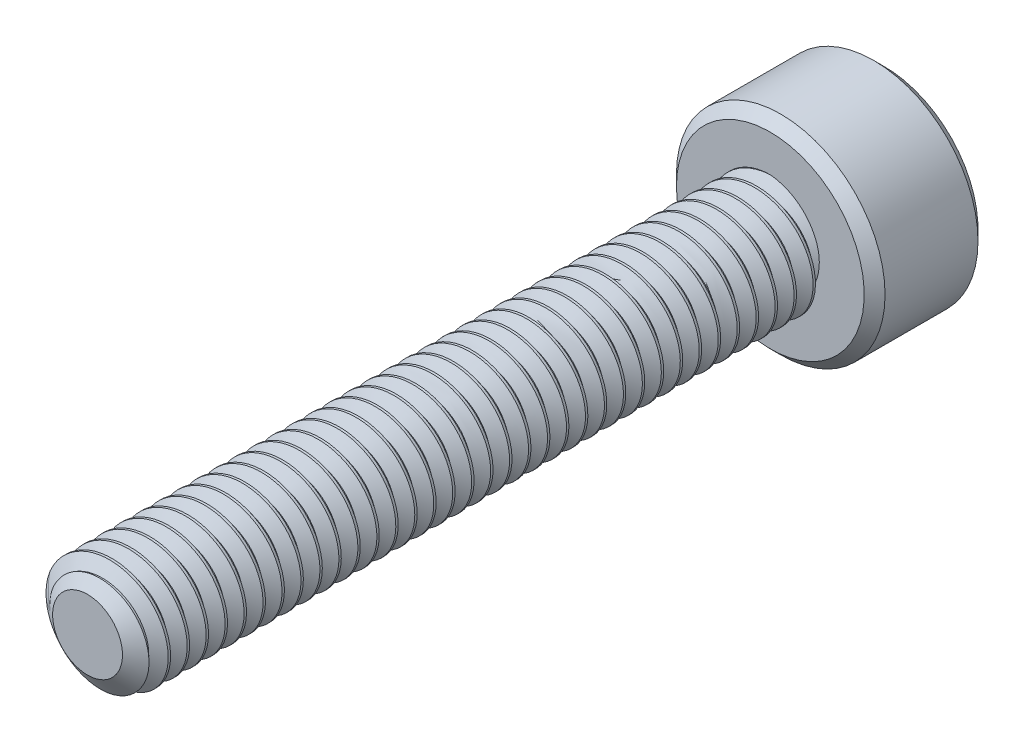
SolidWorks part; units mm, degrees
other "DetailItem1"
ref_plane "Front Plane" through (0, 0, 0) normal (0, 0, 1) x (1, 0, 0)
ref_plane "Top Plane" through (0, 0, 0) normal (0, 1, 0) x (1, 0, 0)
ref_plane "Right Plane" through (0, 0, 0) normal (1, 0, 0) x (0, 0, -1)
sketch "Sketch1" plane through (0, 0, 0) normal (0, 0, 1) x (1, 0, 0)
  circle A0 centre (0, 0) radius 1.5
  dimension "OD" = 3
extrude "Extrude1" add sketch "Sketch1" against normal blind 18
sketch "Sketch2" plane through (0, 0, 0) normal (0, 0, 1) x (1, 0, 0)
  circle A0 centre (0, 0) radius 1.5 construction
  circle A1 centre (0, 0) radius 1.5
curve "Helix/Spiral1" pitch 0.5 height 18.5 turns 37 parameters "pitch"=0.5
sketch "Sketch3" plane through (0, 0, 0) normal (1, 0, 0) x (0, 0, -1)
  line L0 (-0.4375, 1.5) -> (-0.25, 1.1752)
  line L1 (-0.25, 1.1752) -> (-0.1875, 1.1752)
  line L2 (-0.1875, 1.1752) -> (0, 1.5)
  line L3 (-0.4375, 1.5) -> (0, 1.5)
  line L4 (-0.2187, 1.5) -> (-0.2188, 1.1752) construction
  line L5 (-0.3438, 1.3376) -> (-0.0938, 1.3376) construction
  line L6 (0, 1.5) -> (0, -1.5) construction
  dimension "D1" = 0.0625
  dimension "D2" = 0.25
  dimension "D3" = 60
sweep "Cut-Sweep1" cut profiles "Sketch3" path "Helix/Spiral1" align with end faces yes
sketch "Sketch4" plane through (0, 0, 0) normal (1, 0, 0) x (0, 0, -1)
  line L0 (0.4053, 1.5) -> (0, 0.9212)
  line L1 (0, 0.9212) -> (0, 1.5)
  line L2 (0.4053, 1.5) -> (0, 1.5)
  line L3 (-0.4375, 1.5) -> (0, 1.5) construction
  line L4 (0, 0) -> (7.0209, 0) construction
  dimension "D1" = 55
  dimension "D2" = 0.254
revolve "Cut-Revolve1" cut sketch "Sketch4" angle 360 about L4
sketch "Sketch6" plane through (0, 0, -18) normal (0, 0, -1) x (-1, 0, 0)
  circle A0 centre (0, 0) radius 2.75
  dimension "head dia" = 5.5
extrude "Extrude2" add sketch "Sketch6" along normal blind 3
sketch "Sketch7" plane through (0, 0, -21) normal (0, 0, -1) x (-1, 0, 0)
  line L1 (0, 1.4434) -> (-1.25, 0.7217)
  line L2 (-1.25, 0.7217) -> (-1.25, -0.7217)
  line L3 (-1.25, -0.7217) -> (0, -1.4434)
  line L4 (0, -1.4434) -> (1.25, -0.7217)
  line L5 (1.25, -0.7217) -> (1.25, 0.7217)
  line L6 (1.25, 0.7217) -> (0, 1.4434)
  circle A0 centre (0, 0) radius 1.25 construction
  dimension "hex dia" = 2.5
extrude "Cut-Extrude1" cut sketch "Sketch7" against normal blind 1.875
sketch "Sketch8" plane through (0, 0, -21) normal (0, 0, -1) x (-1, 0, 0)
  circle A0 centre (0, 0) radius 1.4434
extrude "Cut-Extrude2" cut sketch "Sketch8" against normal through all draft 45
chamfer "Chamfer1" distance 0.275 angle 45 2 edges at (-2.75, 0, -21) (-2.75, 0, -18)
sketch "Sketch10" plane through (0, 0, -18) normal (0, 0, 1) x (1, 0, 0)
  circle A1 centre (0, 0) radius 1.5
  circle A2 centre (0, 0) radius 1.5
  dimension "D1" = 0
ref_plane "Plane1" through (0, 0, 0) normal (0, 0, 1) x (1, 0, 0)
extrude "partial thread" [suppressed] add sketch "Sketch10" along normal up to surface (4 mm away) separate body
chamfer "Chamfer2" [suppressed] distance 0.06 angle 45
combine bodies "Combine1" [suppressed] operation type add bodies to combine 107 108
sketch "Sketch9" plane through (0, 0, 0) normal (1, 0, 0) x (0, 0, -1)
  line L0 (0, 1.5) -> (0, -1.5) construction
  line L1 (1.25, 1.5) -> (1.25, -1.5) construction
  dimension "D1" = 1.25
equation "\"D3@Helix/Spiral1\" = \"screw length@Extrude1\"+\"pitch@Helix/Spiral1\""
equation "\"D1@Sketch3\" = \"pitch@Helix/Spiral1\"*.125"
equation "\"D2@Sketch3\" = \"pitch@Helix/Spiral1\"*.5"
equation "\"D1@Cut-Extrude1\" = \"hex dia@Sketch7\"*.75"
equation "\"D1@Chamfer1\" = \"head dia@Sketch6\"*.05"
equation "\"D1@Sketch9\" = \"pitch@Helix/Spiral1\"*2.5"
equation "\"D1@Chamfer2\"=\"OD@Sketch1\"*.02"
